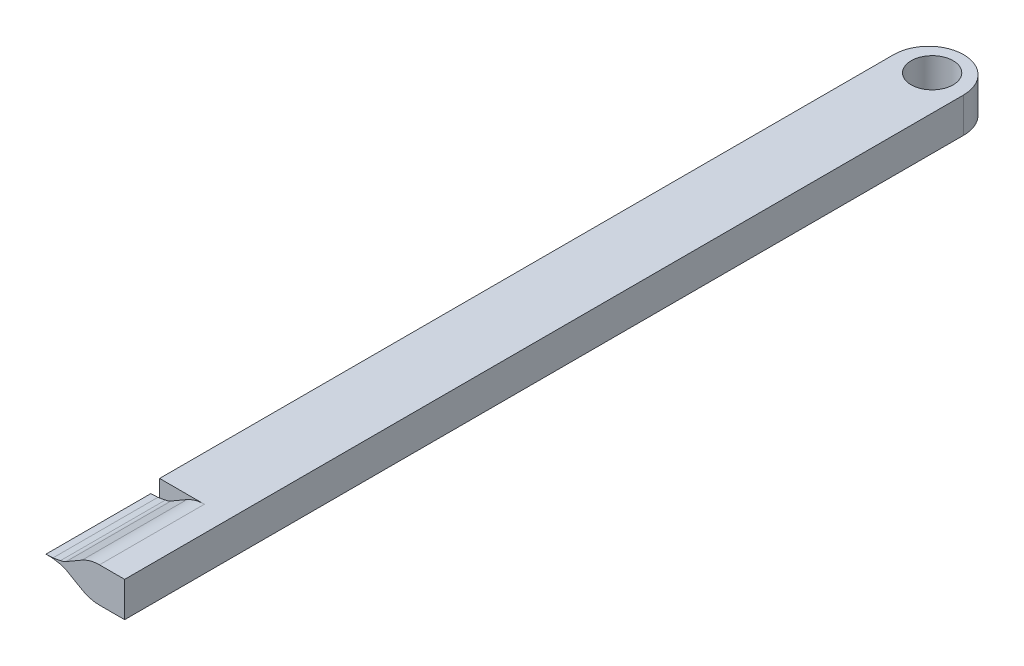
SolidWorks part; units mm, degrees
ref_plane "Front Plane" through (0, 0, 0) normal (0, 0, 1) x (1, 0, 0)
ref_plane "Top Plane" through (0, 0, 0) normal (0, 1, 0) x (1, 0, 0)
ref_plane "Right Plane" through (0, 0, 0) normal (1, 0, 0) x (0, 0, -1)
sketch "Sketch2" plane through (0, 0, 0) normal (0, 0, 1) x (1, 0, 0)
  line L1 (0, 0) -> (20, 0)
  line L2 (0, 0) -> (0, 10)
  line L3 (0, 10) -> (20, 10)
  line L4 (20, 0) -> (20, 10)
  dimension "D1" = 10
  dimension "D2" = 20
extrude "Boss-Extrude1" add sketch "Sketch2" along normal blind 250
sketch "Sketch3" plane through (0, 10, 0) normal (0, 1, 0) x (1, 0, 0)
  line L0 (20, 0) -> (0, 0) construction
  circle A0 centre (10, -9) radius 6
  point P2 (10, 0)
  dimension "D1" = 12
  dimension "D2" = 9
extrude "Cut-Extrude1" cut sketch "Sketch3" against normal blind 30
fillet "Fillet1" radius 10 1 edges at (20, 5, 0)
fillet "Fillet3" radius 10 1 edges at (0, 5, 0)
sketch "Sketch4" plane through (0, 0, 0) normal (-1, 0, 0) x (0, 0, 1)
  line L0 (250, 0) -> (10, 0) construction
  line L1 (220, 0) -> (250, 0)
  line L2 (220, 0) -> (220, 10)
  line L3 (220, 10) -> (250, 10)
  line L4 (250, 0) -> (250, 10)
  dimension "D1" = 30
extrude "Boss-Extrude2" add sketch "Sketch4" along normal blind 2.5
sketch "Sketch5" plane through (0, 0, 250) normal (0, 0, 1) x (1, 0, 0)
  line L0 (-2.5, 5) -> (-0.5, 5.0698)
  line L1 (-2.5, 0) -> (-2.5, 10) construction
  line L2 (-0.5, 5.0698) -> (2.5, 5.5988)
  line L3 (2.5, 5.5988) -> (10.1231, 10)
  line L4 (20, 10) -> (-2.5, 10) construction
  line L5 (10.1231, 10) -> (10.1231, 0)
  line L6 (-2.5, 5) -> (6.83, 5) construction
  line L7 (2.5, 4.4012) -> (10.1231, 0)
  line L8 (-2.5, 5) -> (-0.5, 4.9302)
  line L9 (-0.5, 4.9302) -> (2.5, 4.4012)
  line L10 (-2.5, 5) -> (-2.5, 10)
  line L11 (-2.5, 10) -> (10.1231, 10)
  line L12 (-2.5, 5) -> (-2.5, 0)
  line L13 (-2.5, 0) -> (10.1231, 0)
  point P11 (10.1231, 5)
  line M6 (20, 10) -> (-2.5, 10)
  line M7 (-2.5, 10) -> (-2.5, 0)
  line M8 (-2.5, 0) -> (20, 0)
  dimension "D1" = 3
  dimension "D2" = 2
  dimension "D3" = 2
  dimension "D4" = 10
  dimension "D5" = 30
extrude "Cut-Extrude2" cut sketch "Sketch5" against normal blind 30 contours L2 L3 L0 M6 M7 | L9 L8 L7 M7 M8 region at (2.0452, 7.9866, 250) region at (2.0452, 2.0134, 250)
fillet "Fillet4" radius 5 2 edges at (2.5, 5.5988, 235) (2.5, 4.4012, 235)
fillet "Fillet5" radius 10 2 edges at (10.1231, 0, 235) (10.1231, 10, 235)
